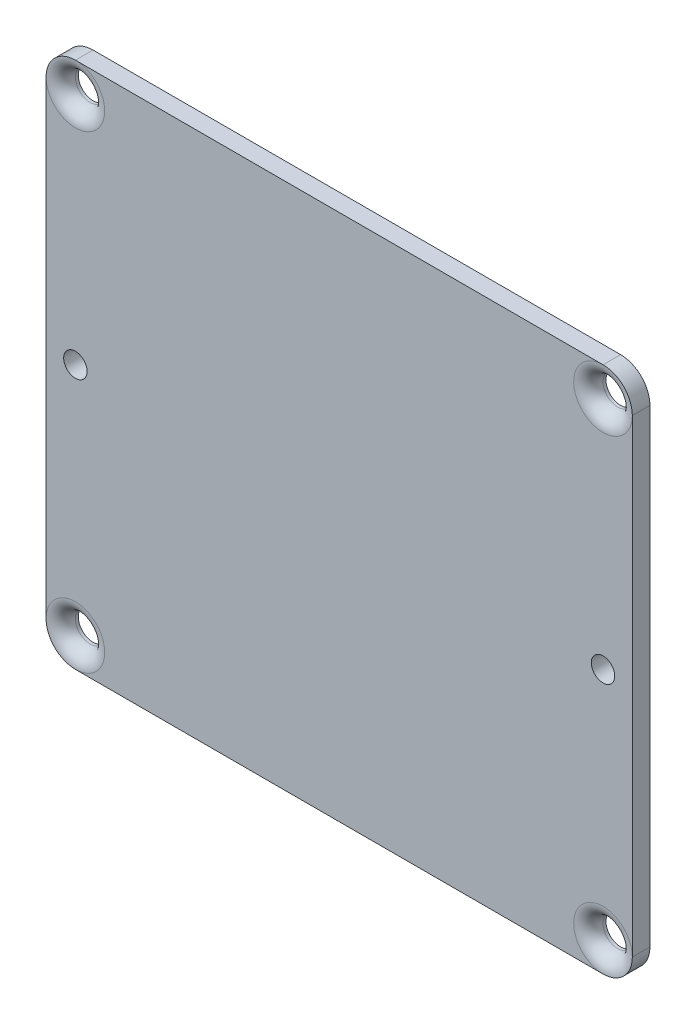
SolidWorks part; units mm, degrees
ref_plane "Front Plane" through (0, 0, 0) normal (0, 0, 1) x (1, 0, 0)
ref_plane "Top Plane" through (0, 0, 0) normal (0, 1, 0) x (1, 0, 0)
ref_plane "Right Plane" through (0, 0, 0) normal (1, 0, 0) x (0, 0, -1)
sketch "Sketch2" plane through (0, 0, 0) normal (0, 0, 1) x (1, 0, 0)
  line L0 (6.35, 57.15) -> (6.35, 114.3) construction
  line L1 (0, 0) -> (127, 0)
  line L2 (0, 0) -> (0, 114.3)
  line L3 (0, 114.3) -> (127, 114.3)
  line L4 (127, 0) -> (127, 114.3)
  line L5 (12.7, 12.7) -> (114.3, 12.7)
  line L6 (12.7, 12.7) -> (12.7, 101.6)
  line L7 (12.7, 101.6) -> (114.3, 101.6)
  line L8 (114.3, 12.7) -> (114.3, 101.6)
  line L9 (6.35, 57.15) -> (6.35, 0) construction
  line L10 (6.35, 57.15) -> (0, 57.15) construction
  line L11 (6.35, 57.15) -> (12.7, 57.15) construction
  line L12 (120.65, 57.15) -> (120.65, 107.95) construction
  line L13 (120.65, 57.15) -> (120.65, 6.35) construction
  line L14 (120.65, 57.15) -> (114.3, 57.15) construction
  line L15 (120.65, 57.15) -> (127, 57.15) construction
  circle A0 centre (6.35, 107.95) radius 3.175
  circle A1 centre (120.65, 107.95) radius 3.175
  circle A2 centre (120.65, 6.35) radius 3.175
  circle A3 centre (6.35, 6.35) radius 3.175
  circle A4 centre (6.35, 57.15) radius 2.54
  circle A5 centre (120.65, 57.15) radius 2.54
  point P21 (120.65, 63.0569)
  point P28 (12.7, 55.5261)
  point P29 (12.7, 57.15)
  point P30 (12.7, 57.15)
  dimension "D7" = 6.35
  dimension "D8" = 6.35
  dimension "D9" = 6.35
  dimension "D10" = 6.35
  dimension "D19" = 5.08
  dimension "D20" = 5.08
  dimension "D1" = 101.6
  dimension "D2" = 88.9
  dimension "D3" = 12.7
  dimension "D4" = 12.7
  dimension "D5" = 12.7
  dimension "D6" = 12.7
  dimension "D11" = 6.35
  dimension "D12" = 6.35
  dimension "D13" = 6.35
  dimension "D14" = 6.35
  dimension "D15" = 6.35
  dimension "D16" = 6.35
  dimension "D17" = 6.35
  dimension "D18" = 6.35
extrude "Boss-Extrude2" add sketch "Sketch2" along normal blind 3.81 contours L2 L1 L4 L3 | A4 | A5 | A1 | A0 | A3 | A2
fillet "Fillet1" radius 3.175 4 edges at (9.525, 6.35, 3.81) (123.825, 107.95, 3.81) (9.525, 107.95, 3.81) (123.825, 6.35, 3.81)
fillet "Fillet2" radius 6.35 4 edges at (127, 114.3, 1.905) (127, 0, 1.905) (0, 0, 1.905) (0, 114.3, 1.905)
